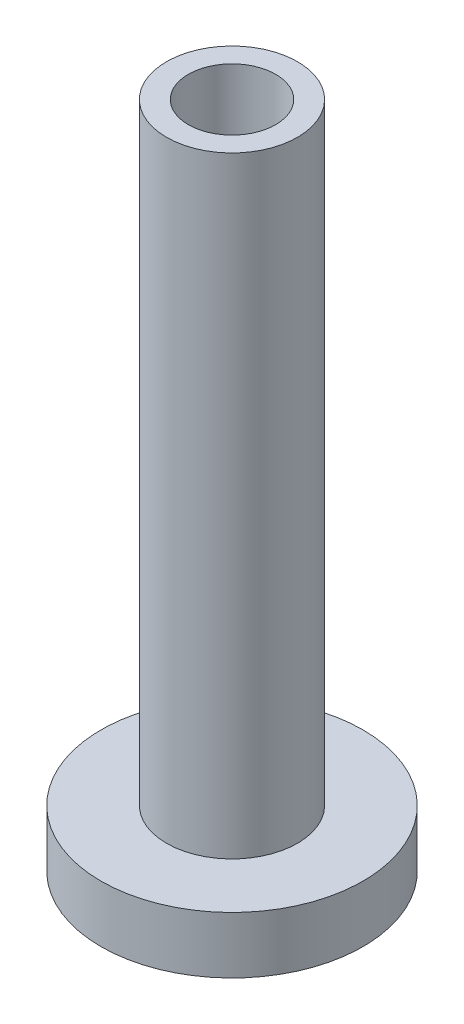
SolidWorks part; units mm, degrees
ref_plane "前视基准面" through (0, 0, 0) normal (0, 0, 1) x (1, 0, 0)
ref_plane "上视基准面" through (0, 0, 0) normal (0, 1, 0) x (1, 0, 0)
ref_plane "右视基准面" through (0, 0, 0) normal (1, 0, 0) x (0, 0, -1)
other "Configuration Table"
sketch "草图1" plane through (0, 0, 0) normal (0, 1, 0) x (1, 0, 0)
  line L1 (1.1547, 0) -> (0.5774, 1)
  line L2 (0.5774, 1) -> (-0.5774, 1)
  line L3 (-0.5774, 1) -> (-1.1547, 0)
  line L4 (-1.1547, 0) -> (-0.5774, -1)
  line L5 (-0.5774, -1) -> (0.5774, -1)
  line L6 (0.5774, -1) -> (1.1547, 0)
  circle A0 centre (0, 0) radius 3
  circle A1 centre (0, 0) radius 1 construction
  dimension "D1" = 6
  dimension "D2" = 2
extrude "凸台-拉伸1" add sketch "草图1" along normal blind 1.3 contours L5 L6 L1 L2 L3 L4 | A0 L6 L5 L4 L3 L2 L1 region at (0, 0, 0) region at (-2.9151, 0, 0)
extrude "切除-拉伸1" cut sketch "草图1<3>" along normal blind 0.6 contours L5 L6 L1 L2 L3 L4 region at (0, 0, 0)
sketch "草图1<3>" plane through (0, 0, 0) normal (0, 1, 0) x (1, 0, 0) same geometry as "草图1"
sketch "草图2" plane through (0, 1.3, 0) normal (0, 1, 0) x (1, 0, 0)
  circle A0 centre (0, 0) radius 1.5
  circle A1 centre (0, 0) radius 1
  dimension "D1" = 3
  dimension "D2" = 2
extrude "凸台-拉伸2" add sketch "草图2" along normal blind 14
